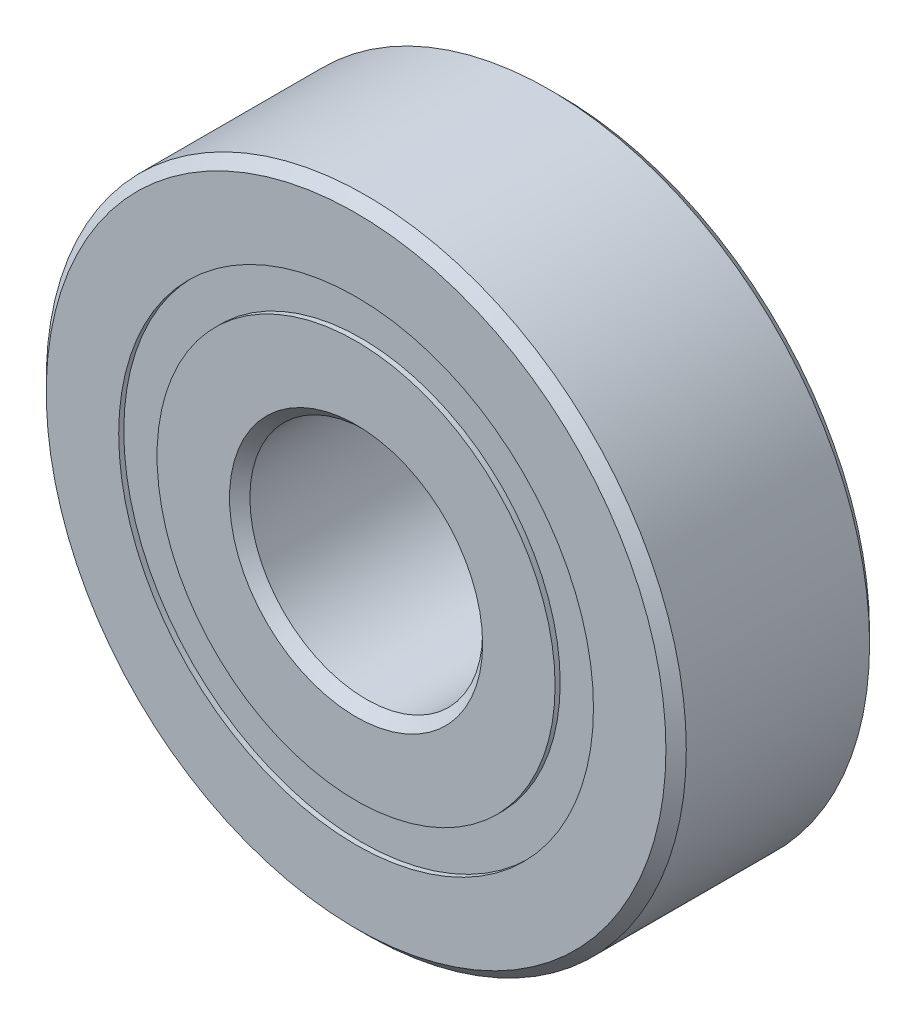
SolidWorks part; units mm, degrees
ref_plane "Front Plane" through (0, 0, 0) normal (0, 0, 1) x (1, 0, 0)
ref_plane "Top Plane" through (0, 0, 0) normal (0, 1, 0) x (1, 0, 0)
ref_plane "Right Plane" through (0, 0, 0) normal (1, 0, 0) x (0, 0, -1)
sketch "Sketch1" plane through (0, 0, 0) normal (1, 0, 0) x (0, 0, -1)
  line L0 (-3.5, 0) -> (3.5, 0) construction
  line L1 (0, 11) -> (0, -11) construction
  line L2 (3.15, 11) -> (-3.15, 11)
  line L3 (-3.15, 11) -> (-3.5, 10.65)
  line L4 (-3.5, 10.65) -> (-3.5, 8.1593)
  line L5 (-3.5, 8.1593) -> (-1.5556, 8.1593)
  line L6 (3.5, 8.1593) -> (1.5556, 8.1593)
  line L7 (3.5, 10.65) -> (3.5, 8.1593)
  line L8 (3.15, 11) -> (3.5, 10.65)
  line L9 (0, 11) -> (0, 7.5) construction
  line L10 (0, 7.5) -> (0, 4) construction
  arc A0 (-1.5556, 8.1593) -> (1.5556, 8.1593) centre (0, 7.5) cw
  point P14 (0, 4)
  dimension "D3" = 3.1111
  dimension "D1" = 45
  dimension "Width" = 7
  dimension "OD" = 22
  dimension "D2" = 0.35
  dimension "Shaft Dia" = 8
  dimension "D4" = 0.6593
revolve "Revolve1" add sketch "Sketch1" angle 360 about L0
sketch "Sketch3" plane through (0, 0, 0) normal (1, 0, 0) x (0, 0, -1)
  line L0 (-3.5, 6.8407) -> (-1.5556, 6.8407)
  line L1 (0, 11) -> (0, -11) construction
  line L2 (-3.5, 10.65) -> (-3.5, 8.1593) construction
  line L3 (-3.5, 6.8407) -> (-3.5, 4.35)
  line L4 (-3.15, 11) -> (-3.5, 10.65) construction
  line L5 (-3.5, 4.35) -> (-3.15, 4)
  line L6 (-3.15, 4) -> (3.15, 4)
  line L7 (3.15, 11) -> (3.15, -11) construction
  line L8 (3.15, 4) -> (3.5, 4.35)
  line L9 (3.5, -10.65) -> (3.5, 10.65) construction
  line L10 (3.5, 4.35) -> (3.5, 6.8407)
  line L11 (3.5, 6.8407) -> (1.5556, 6.8407)
  line L13 (3.15, 11) -> (3.5, 10.65) construction
  arc A0 (1.5556, 8.1593) -> (-1.5556, 8.1593) centre (0, 7.5) ccw construction
  arc A1 (1.5556, 6.8407) -> (-1.5556, 6.8407) centre (0, 7.5) cw
revolve "Revolve3" add sketch "Sketch3" angle 360 about L0
sketch "Sketch4" plane through (0, 0, 0) normal (1, 0, 0) x (0, 0, -1)
  line L0 (-1.6895, 7.5) -> (1.6895, 7.5)
  arc A2 (-1.6895, 7.5) -> (1.6895, 7.5) centre (0, 7.5) cw
  arc A3 (1.5556, 8.1593) -> (-1.5556, 8.1593) centre (0, 7.5) ccw construction
revolve "Revolve4" add sketch "Sketch4" angle 360 about L0
ref_axis "Axis1" through (0, 0, -3.5) along (0, 0, 1)
pattern_circular "CirPattern1" count 14 every 25.714 about axis through (0, 0, -3.5) along (0, 0, 1) of bodies 104
sketch "Sketch6" plane through (0, 0, 0) normal (1, 0, 0) x (0, 0, -1)
  line L0 (-3.5, 8.1593) -> (-1.5556, 8.1593) construction
  line L1 (-3.325, 8.1593) -> (-1.6895, 8.1593)
  line L2 (-3.325, 8.1593) -> (-3.325, 6.8407)
  line L3 (-3.325, 6.8407) -> (-1.6895, 6.8407)
  line L4 (-1.6895, 8.1593) -> (-1.6895, 6.8407)
  line L5 (-3.5, 6.8407) -> (-1.5556, 6.8407) construction
  line L6 (3.5, 8.1593) -> (1.5556, 8.1593) construction
  line L7 (3.325, 8.1593) -> (1.6895, 8.1593)
  line L8 (3.325, 8.1593) -> (3.325, 6.8407)
  line L9 (3.325, 6.8407) -> (1.6895, 6.8407)
  line L10 (1.6895, 8.1593) -> (1.6895, 6.8407)
  line L11 (3.5, 6.8407) -> (1.5556, 6.8407) construction
  line L12 (-3.15, 11) -> (-3.5, 10.65) construction
  point P18 (-3.325, 10.825)
revolve "Revolve5" add sketch "Sketch6" angle 360 about L0
equation "\"D2@Sketch1\" = \"Width@Sketch1\"*.05"
equation "\"D3@Sketch1\" = \"Width@Sketch1\"/2.25"
equation "\"D4@Sketch1\" = (((\"OD@Sketch1\"-\"Width@Sketch1\")/2)/3.25)/3.5"
equation "\"D2@CirPattern1\" = 360/\"Balls@CirPattern1\""
